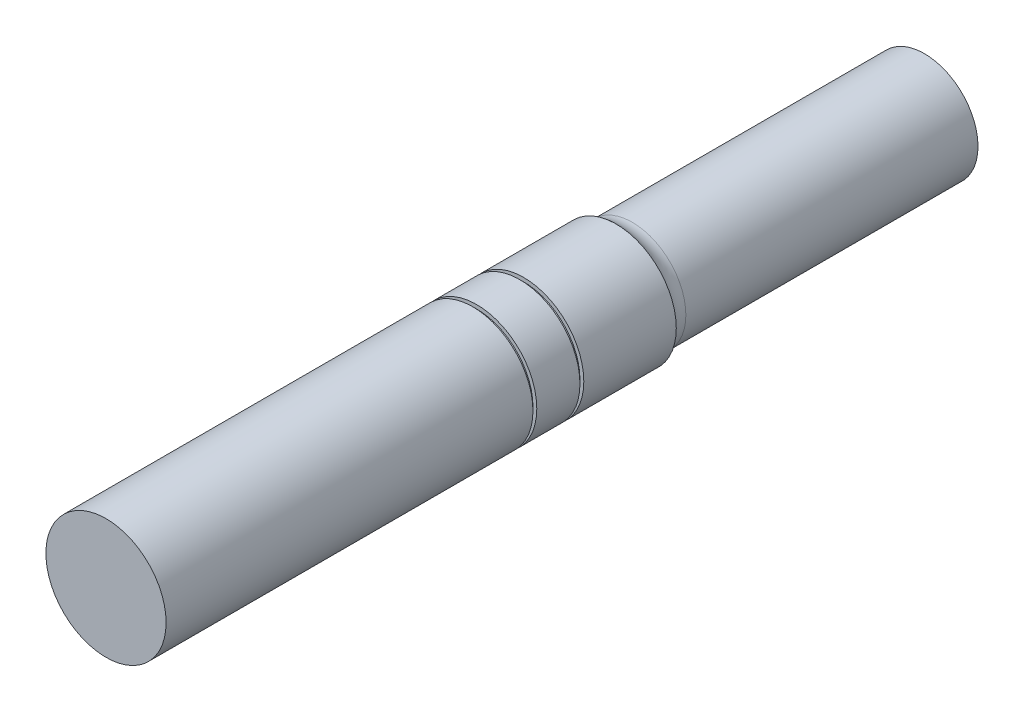
SolidWorks part; units mm, degrees
material "O1 Steel"
ref_plane "Alzado" through (0, 0, 0) normal (0, 0, 1) x (1, 0, 0)
ref_plane "Planta" through (0, 0, 0) normal (0, 1, 0) x (1, 0, 0)
ref_plane "Vista lateral" through (0, 0, 0) normal (1, 0, 0) x (0, 0, -1)
sketch "Croquis1" plane through (0, 0, 0) normal (1, 0, 0) x (0, 0, -1)
  line L0 (-127, 0) -> (127, 0) construction
  line L1 (-13.4874, 0) -> (-13.4874, 1.9812)
  line L3 (0.1524, 1.9812) -> (0.1524, 1.8542)
  line L4 (0.1524, 1.8542) -> (0.2794, 1.8542)
  line L5 (0.2794, 1.8542) -> (0.2794, 1.9812)
  line L10 (0.2794, 1.9812) -> (3.3274, 1.9812)
  line L11 (3.3274, 1.9812) -> (3.3274, 1.7653)
  line L12 (3.3274, 1.7653) -> (13.4874, 1.7653)
  line L13 (13.4874, 1.7653) -> (13.4874, 0)
  line L14 (13.4874, 0) -> (-13.4874, 0)
  line L15 (0.1524, 1.9812) -> (-1.27, 1.9812)
  line L16 (-1.27, 1.9812) -> (-1.27, 1.8542)
  line L17 (-1.27, 1.8542) -> (-1.397, 1.8542)
  line L18 (-1.397, 1.8542) -> (-1.397, 1.9812)
  line L19 (-1.397, 1.9812) -> (-13.4874, 1.9812)
  point P7 (0, 1.85)
  point P18 (0, 0)
  dimension "D1" = 254
  dimension "D2" = 3.9624
  dimension "D3" = 26.9748
  dimension "D4" = 3.5306
  dimension "D5" = 10.16
  dimension "D6" = 3.048
  dimension "D7" = 0.127
  dimension "D8" = 0.127
  dimension "D9" = 1.5494
revolve "Revolución1" add sketch "Croquis1" angle 360 about L0
fillet "Redondeo1" radius 0.762 1 edges at (1.7653, 0, -3.3274)
sketch "Croquis2" plane through (0, 0, -13.4874) normal (0, 0, -1) x (-1, 0, 0)
  point P0 (0, 0)
hole_wizard "Taladro de margen para #101" positions "Croquis2" profile "Croquis3" hole size "#10" standard "Ansi Inch"
sketch "Croquis3" plane through (0, 0, -13.4874) normal (1, 0, 0) x (0, 1, 0)
  line L0 (0, 0) -> (0, 1.5706)
  line L1 (0, 1.5706) -> (0.9652, 0.9906)
  line L2 (0.9652, 0.9906) -> (0.9652, 0)
  line L5 (0.9652, 0) -> (0, 0)
  line L10 (0, 1.5706) -> (-0.9652, 0.9906) construction
  line L11 (0, -6.35) -> (0, 107.95) construction
  dimension "Diámetro de taladro" = 1.9304
  dimension "Profundidad de taladro" = 0.9906
  dimension "Ángulo de perforador" = 118
chamfer "Chaflán1" distance 0.7937 angle 30 1 edges at (-0.9652, 0, -13.4874) first distance on face at (-0.9652, 0, -13.4874)
